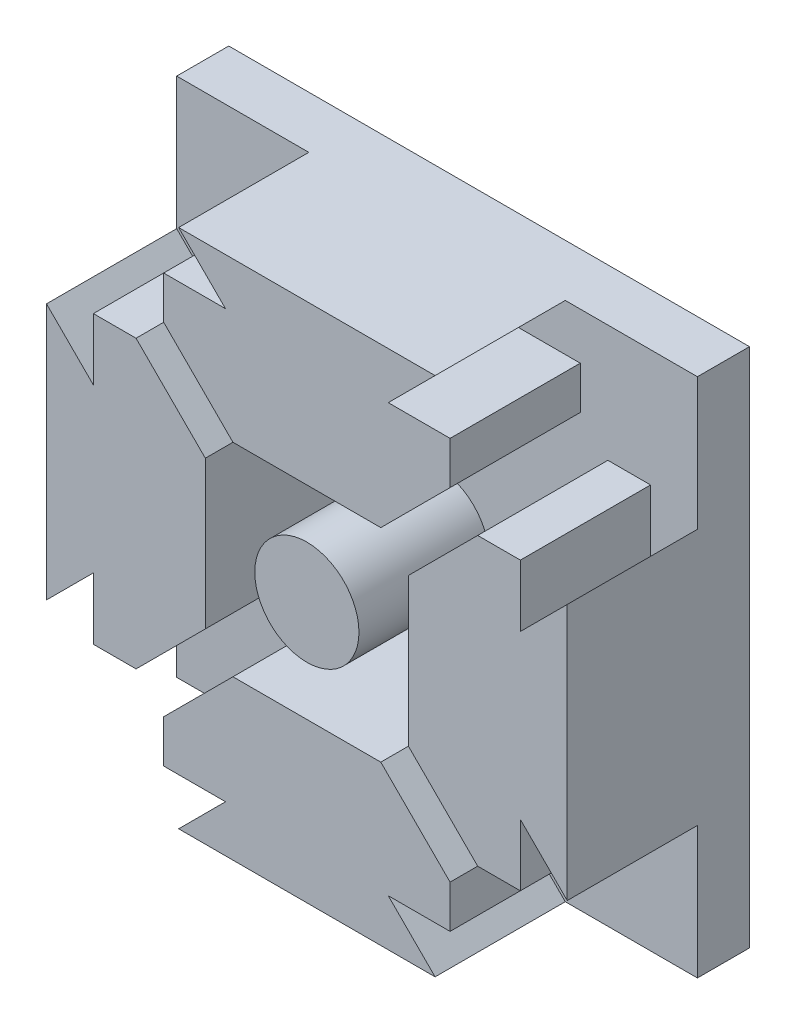
SolidWorks part; units mm, degrees
ref_plane "Front Plane" through (0, 0, 0) normal (0, 0, 1) x (1, 0, 0)
ref_plane "Top Plane" through (0, 0, 0) normal (0, 1, 0) x (1, 0, 0)
ref_plane "Right Plane" through (0, 0, 0) normal (1, 0, 0) x (0, 0, -1)
sketch "Sketch1" plane through (0, 0, 0) normal (0, 0, 1) x (1, 0, 0)
  line L0 (-4.925, 10) -> (-3.125, 8.2)
  line L1 (-10, -10) -> (10, -10)
  line L2 (-10, -10) -> (-10, 10)
  line L3 (-10, 10) -> (10, 10)
  line L4 (10, -10) -> (10, 10)
  line L5 (-10, -10) -> (10, 10) construction
  line L6 (-10, 10) -> (10, -10) construction
  line L7 (-3.125, 8.2) -> (-5.5, 8.2)
  line L8 (-5.5, 8.2) -> (-5.5, 6.5607)
  line L9 (-5.5, 6.5607) -> (-2.8393, 3.9)
  line L10 (-2.8393, 3.9) -> (2.8393, 3.9)
  line L11 (0, -55) -> (0, 55) construction
  line L12 (-10, 4.925) -> (-8.2, 3.125)
  line L13 (-8.2, 3.125) -> (-8.2, 5.5)
  line L14 (-8.2, 5.5) -> (-6.5607, 5.5)
  line L15 (-6.5607, 5.5) -> (-3.9, 2.8393)
  line L16 (-3.9, 2.8393) -> (-3.9, -2.8393)
  line L17 (55, 0) -> (-55, 0) construction
  line L18 (-4.925, -10) -> (-3.125, -8.2)
  line L19 (-3.125, -8.2) -> (-5.5, -8.2)
  line L20 (-5.5, -8.2) -> (-5.5, -6.5607)
  line L21 (-5.5, -6.5607) -> (-2.8393, -3.9)
  line L22 (-2.8393, -3.9) -> (2.8393, -3.9)
  line L23 (-6.5607, -5.5) -> (-3.9, -2.8393)
  line L24 (-8.2, -5.5) -> (-6.5607, -5.5)
  line L25 (-8.2, -3.125) -> (-8.2, -5.5)
  line L26 (-10, -4.925) -> (-8.2, -3.125)
  line L27 (4.925, -10) -> (3.125, -8.2)
  line L28 (5.5, -8.2) -> (5.5, -6.5607)
  line L29 (3.125, -8.2) -> (5.5, -8.2)
  line L30 (5.5, -6.5607) -> (2.8393, -3.9)
  line L31 (8.2, -5.5) -> (6.5607, -5.5)
  line L32 (6.5607, -5.5) -> (3.9, -2.8393)
  line L33 (8.2, -3.125) -> (8.2, -5.5)
  line L34 (10, -4.925) -> (8.2, -3.125)
  line L35 (10, 4.925) -> (8.2, 3.125)
  line L36 (8.2, 3.125) -> (8.2, 5.5)
  line L37 (8.2, 5.5) -> (6.5607, 5.5)
  line L38 (6.5607, 5.5) -> (3.9, 2.8393)
  line L39 (3.9, 2.8393) -> (3.9, -2.8393)
  line L40 (5.5, 6.5607) -> (2.8393, 3.9)
  line L41 (5.5, 8.2) -> (5.5, 6.5607)
  line L42 (3.125, 8.2) -> (5.5, 8.2)
  line L43 (4.925, 10) -> (3.125, 8.2)
  circle A0 centre (0, 0) radius 2
  point P0 (0, 0)
  point P29 (-3.9, 0)
  point P38 (0, -3.9)
  point P49 (0, 3.9)
  dimension "D2" = 4
  dimension "D1" = 20
  dimension "D3" = 3.125
  dimension "D4" = 5.5
  dimension "D5" = 45
  dimension "D6" = 4.3
  dimension "D7" = 1.8
  dimension "D8" = 1.5
  dimension "D9" = 3.125
  dimension "D10" = 5.5
  dimension "D11" = 1.8
  dimension "D12" = 4.3
extrude "Boss-Extrude1" add sketch "Sketch1" along normal blind 5 contours L43 L3 L0 L7 L8 L9 L10 L40 L41 L42 | A0 | L38 L39 L32 L31 L33 L34 L4 L35 L36 L37 | L2 L26 L25 L24 L23 L16 L15 L14 L13 L12 | L28 L30 L22 L21 L20 L19 L18 L1 L27 L29 region at (0, 7.039, 0) region at (-7.039, 0, 0) region at (7.039, 0, 0) region at (0, -7.039, 0) region at (0, 0, 0)
extrude "Boss-Extrude2" add sketch "Sketch1<3>" against normal blind 2 contours L3 L4 L1 L2
sketch "Sketch1<3>" plane through (0, 0, 0) normal (0, 0, 1) x (1, 0, 0) same geometry as "Sketch1"
